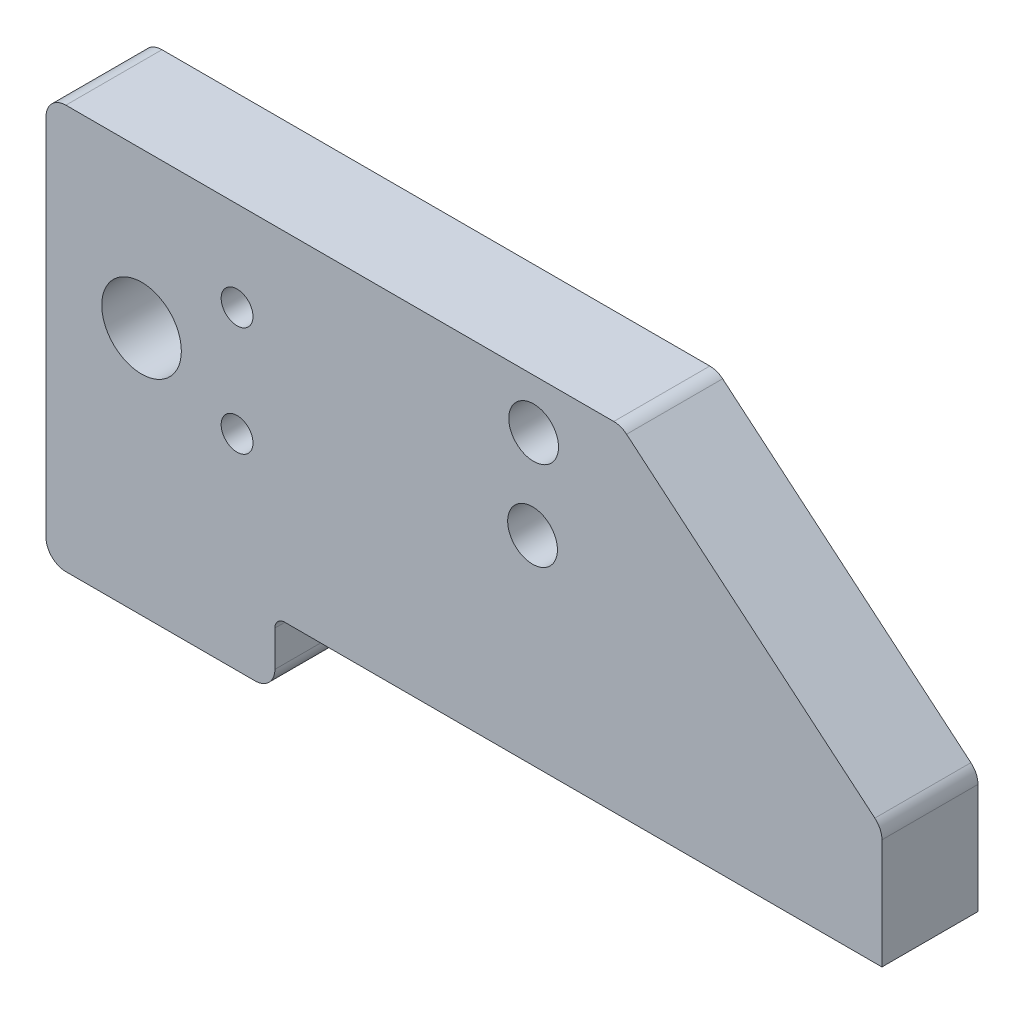
SolidWorks part; units mm, degrees
material "6061-T4 (SS)"
ref_plane "Front" through (0, 0, 0) normal (0, 0, 1) x (1, 0, 0)
ref_plane "Top" through (0, 0, 0) normal (0, 1, 0) x (1, 0, 0)
ref_plane "Right" through (0, 0, 0) normal (1, 0, 0) x (0, 0, -1)
sketch "Sketch1" plane through (0, 0, 0) normal (0, 0, 1) x (1, 0, 0)
  line L0 (-4.4454, 10) -> (-4.4454, 17) construction
  line L1 (0, 0) -> (-8.8907, 0)
  line L2 (0, 0) -> (0, 17) construction
  line L3 (0, 17) -> (-8.8907, 17)
  line L4 (-8.8907, 0) -> (-8.8907, 17)
  line L5 (-4.4454, 10) -> (-8.8907, 10) construction
  line L6 (-4.4454, 10) -> (0, 10) construction
  line L7 (0, 17) -> (13.1093, 6)
  line L8 (13.1093, 6) -> (13.1093, 0)
  line L9 (13.1093, 0) -> (0, 0)
  line L10 (-8.8907, 0) -> (-17.3907, 0)
  line L11 (-17.3907, 0) -> (-17.3907, -3.3)
  line L12 (-17.3907, -3.3) -> (-28.8907, -3.3)
  line L13 (-28.8907, -3.3) -> (-28.8907, 17)
  line L14 (-28.8907, 17) -> (-8.8907, 17)
  line L16 (-28.8907, 17) -> (-17.3907, 17)
  line L17 (-28.8907, 17) -> (-28.8907, 19)
  line L18 (-28.8907, 19) -> (-17.3907, 19)
  line L19 (-17.3907, 17) -> (-17.3907, 19)
  circle A0 centre (-24.0907, 9.2) radius 2
  dimension "D3" = 10
  dimension "D12" = 4
  dimension "D2" = 17
  dimension "D4" = 6
  dimension "D5" = 22
  dimension "D6" = 230
  dimension "D7" = 11.5
  dimension "D8" = 3.3
  dimension "D9" = 2
  dimension "D10" = 12.5
  dimension "D11" = 4.8
  dimension "D13" = 20
extrude "Boss-Extrude1" add sketch "Sketch1" along normal blind 4.826 contours L9 L8 L7 L3 L4 L1 region at (0.5258, 7.3457, 0)
sketch "Sketch_baseplate_mounting" plane through (0, 0, 0) normal (0, -1, 0) x (-1, 0, 0)
  line L0 (8.8907, -4.826) -> (8.8907, 0) construction
  line L1 (1.8907, -2.413) -> (8.8907, -2.413) construction
  line L2 (-13.1093, -2.413) -> (-10.1093, -2.413) construction
  line L4 (-13.1093, -4.826) -> (-13.1093, 0) construction
  dimension "D1" = 7
  dimension "D2" = 3
hole_wizard "M3x0.5 Tapped Hole1" positions "Sketch8" profile "Sketch10" tap size "M3x0.5" standard "ANSI Metric" end condition through all
sketch "Sketch8" plane through (0, 0, 4.826) normal (0, 0, 1) x (1, 0, 0)
  point P0 (-4.4454, 10)
sketch "Sketch10" plane through (-4.4454, 10, 4.826) normal (1, 0, 0) x (0, -1, 0)
  line L0 (0, 0) -> (0, 4.826)
  line L1 (0, 4.826) -> (1.25, 4.826)
  line L2 (1.25, 4.826) -> (1.25, 0)
  line L5 (1.25, 0) -> (0, 0)
  line L11 (0, -6.35) -> (0, 107.95) construction
  dimension "Thru Tap Drill Dia." = 2.5
  dimension "Thru Tap Drill Depth" = 4.826
cosmetic thread "Hole Thread2" parameters "D2"=3
hole_wizard "Tap Drill for M3x0.5 Tap1" positions "3DSketch1" profile "Sketch5" hole size "M3x0.5" standard "ANSI Metric"
sketch3d "3DSketch1"
  point P0 (-1.8907, 0, 2.413)
  point P3 (10.1093, 0, 2.413)
sketch "Sketch5" plane through (-1.8907, 0, 2.413) normal (1, 0, 0) x (0, 0, -1)
  line L0 (0, 0) -> (0, 5.7511)
  line L1 (0, 5.7511) -> (1.25, 5)
  line L2 (1.25, 5) -> (1.25, 0)
  line L5 (1.25, 0) -> (0, 0)
  line L10 (0, 5.7511) -> (-1.25, 5) construction
  line L11 (0, -6.35) -> (0, 107.95) construction
  dimension "Hole Dia." = 2.5
  dimension "Hole Depth" = 5
  dimension "Drill Angle" = 118
sketch "Sketch_chipper_mounting" plane through (0, 0, 4.826) normal (0, 0, 1) x (1, 0, 0)
  line L0 (5.5546, 0) -> (5.5546, 4.5) construction
  line L1 (13.1093, 0) -> (-8.8907, 0) construction
  circle A1 centre (-4.4454, 10) radius 1.25 construction
  dimension "D1" = 4.5
  dimension "D2" = 10
extrude "Boss-Extrude2" add sketch "Sketch1<3>" along normal up to surface (4.826 mm away) contours L14 L13 L12 L11 L10 L4 region at (-19.1533, 7.4217, 0) up to face at (-3.1954, 10, 4.826)
sketch "Sketch1<3>" plane through (0, 0, 0) normal (0, 0, 1) x (1, 0, 0) same geometry as "Sketch1"
hole_wizard "M3x0.5 Tapped Hole2" positions "Sketch13" profile "Sketch14" tap size "M3x0.5" standard "ANSI Metric" end condition through all
sketch "Sketch13" plane through (0, 0, 4.826) normal (0, 0, 1) x (1, 0, 0)
  line L0 (-24.0907, 9.2) -> (-4.3907, 9.2) construction
  line L1 (-4.3907, 9.2) -> (-4.3907, 14.5) construction
  point P5 (-4.3907, 14.5)
  dimension "D1" = 19.7
  dimension "D2" = 5.3
cosmetic thread "Hole Thread1" parameters "D2"=3
sketch "Sketch14" plane through (-4.3907, 14.5, 4.826) normal (1, 0, 0) x (0, -1, 0)
  line L0 (0, 0) -> (0, 4.826)
  line L1 (0, 4.826) -> (1.25, 4.826)
  line L2 (1.25, 4.826) -> (1.25, 0)
  line L5 (1.25, 0) -> (0, 0)
  line L11 (0, -6.35) -> (0, 107.95) construction
  dimension "Thru Tap Drill Dia." = 2.5
  dimension "Thru Tap Drill Depth" = 4.826
fillet "Fillet1" radius 1 5 edges at (-28.8907, 17, 2.413) (-17.3907, -3.3, 2.413) (-28.8907, -3.3, 2.413) (13.1093, 6, 2.413) (0, 17, 2.413)
hole_wizard "M2 Tapped Holes" positions "Sketch11" profile "Sketch12" legacy
sketch "Sketch11" plane through (0, 0, 4.826) normal (0, 0, 1) x (1, 0, 0)
  line L0 (-17.3907, 7) -> (-19.2907, 7) construction
  line L2 (-19.2907, 7) -> (-19.2907, -3.3) construction
  line L5 (-19.2907, 7) -> (-19.2907, 12.5) construction
  line L7 (-25.6407, 12.5) -> (-12.9407, 12.5) construction
  line L8 (-18.3907, -3.3) -> (-27.8907, -3.3) construction
  point P0 (-19.2907, 12.5)
  point P2 (-19.2907, 7)
  dimension "D1" = 10.3
  dimension "D2" = 1.9
  dimension "D3" = 12.7
  dimension "D4" = 15.8
sketch "Sketch12" plane through (-19.2907, 12.5, 4.826) normal (1, 0, 0) x (0, -1, 0)
  line L0 (0, 0) -> (0, 4.825)
  line L1 (0, 4.825) -> (0.8, 4.825)
  line L2 (0.8, 4.825) -> (0.8, 0)
  line L3 (0.8, 0) -> (0, 0)
  line L4 (0, 110) -> (0, -10) construction
  dimension "Diameter" = 1.6
  dimension "Depth" = 4.825
fillet "Fillet2" radius 0.5 1 edges at (-17.3907, 0, 2.413)
